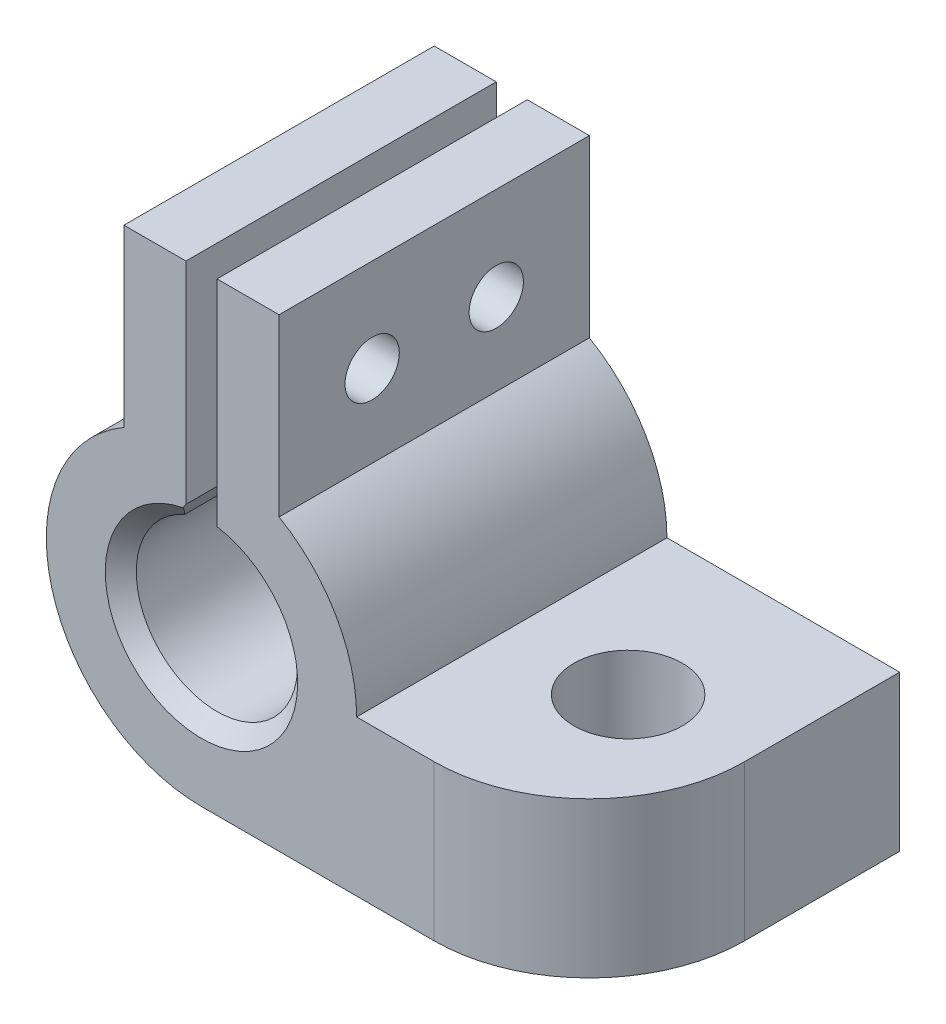
SolidWorks part; units mm, degrees
ref_plane "Płaszczyzna przednia" through (0, 0, 0) normal (0, 0, 1) x (1, 0, 0)
ref_plane "Płaszczyzna górna" through (0, 0, 0) normal (0, 1, 0) x (1, 0, 0)
ref_plane "Płaszczyzna prawa" through (0, 0, 0) normal (1, 0, 0) x (0, 0, -1)
sketch "Szkic1" plane through (0, 0, 0) normal (0, 0, 1) x (1, 0, 0)
  line L0 (-1, 5.1029) -> (-1, 9.9499)
  line L1 (1, 5.1029) -> (1, 9.9499)
  line L2 (0, 0) -> (0, 18.1037) construction
  line L3 (-1, 9.9499) -> (-1, 19.9499)
  line L4 (1, 9.9499) -> (1, 19.9499)
  line L5 (1, 19.9499) -> (5, 19.9499)
  line L6 (5, 19.9499) -> (5, 8.6603)
  line L7 (-1, 19.9499) -> (-5, 19.9499)
  line L8 (-5, 19.9499) -> (-5, 8.6603)
  circle A0 centre (0, 0) radius 5.2
  circle A1 centre (0, 0) radius 10
  dimension "D1" = 10.4
  dimension "D2" = 20
  dimension "D3" = 2
  dimension "D4" = 4
  dimension "D5" = 10
extrude "Dodanie-wyciągnięcie1" add sketch "Szkic1" along normal blind 20 contours A1 L1 A0 L0 | A1 L3 L7 L8 | A1 L6 L5 L4
chamfer "Sfazowanie1" distance 1 angle 45 3 edges at (0, -5.2, 20) (1, 5.1029, 10) (-1, 5.1029, 10)
sketch "Szkic2" plane through (5, 0, 0) normal (1, 0, 0) x (0, 0, -1)
  line L0 (-20, 19.9499) -> (-20, 8.6603) construction
  line L1 (-20, 19.9499) -> (0, 19.9499) construction
  circle A0 centre (-14, 13.9499) radius 1.75
  circle A1 centre (-6, 13.9499) radius 1.75
  dimension "D1" = 3.5
  dimension "D2" = 8
  dimension "D3" = 6
  dimension "D4" = 6
extrude "Wytnij-wyciągnięcie1" cut sketch "Szkic2" against normal blind 10
sketch "Szkic3" plane through (-5, 0, 0) normal (-1, 0, 0) x (0, 0, 1)
  line L1 (9.4641, 13.9499) -> (7.7321, 16.9499)
  line L2 (7.7321, 16.9499) -> (4.2679, 16.9499)
  line L3 (4.2679, 16.9499) -> (2.5359, 13.9499)
  line L4 (2.5359, 13.9499) -> (4.2679, 10.9499)
  line L5 (4.2679, 10.9499) -> (7.7321, 10.9499)
  line L6 (7.7321, 10.9499) -> (9.4641, 13.9499)
  line L7 (10.5359, 13.9499) -> (12.2679, 10.9499)
  line L8 (12.2679, 10.9499) -> (15.7321, 10.9499)
  line L9 (15.7321, 10.9499) -> (17.4641, 13.9499)
  line L10 (17.4641, 13.9499) -> (15.7321, 16.9499)
  line L11 (15.7321, 16.9499) -> (12.2679, 16.9499)
  line L12 (12.2679, 16.9499) -> (10.5359, 13.9499)
  circle A0 centre (14, 13.9499) radius 1.75 construction
  circle A1 centre (6, 13.9499) radius 1.75 construction
  circle A2 centre (14, 13.9499) radius 1.75
  circle A3 centre (6, 13.9499) radius 1.75
  circle A4 centre (6, 13.9499) radius 3 construction
  circle A5 centre (14, 13.9499) radius 3 construction
  dimension "D1" = 6
extrude "Wytnij-wyciągnięcie2" cut sketch "Szkic3" against normal blind 1
sketch "Szkic4" plane through (0, 0, 20) normal (0, 0, 1) x (1, 0, 0)
  line L0 (0, -10) -> (25, -10)
  line L1 (25, -10) -> (25, 0)
  line L2 (25, 0) -> (10, 0)
  arc A0 (-5, 8.6603) -> (5, 8.6603) centre (0, 0) ccw construction
  arc A1 (-5, 8.6603) -> (5, 8.6603) centre (0, 0) ccw
  arc M8 (-5, 8.6603) -> (5, 8.6603) centre (0, 0) ccw
  dimension "D1" = 25
extrude "Dodanie-wyciągnięcie2" add sketch "Szkic4" against normal blind 20 contours L1 L2 L0 M8
sketch "Szkic5" plane through (0, 0, 0) normal (0, 1, 0) x (1, 0, 0)
  line L0 (25, -10) -> (23.319, -10) construction
  line L1 (25, 0) -> (25, -20) construction
  line L2 (17.5, 0) -> (17.5, -3.2931) construction
  line L3 (25, 0) -> (10, 0) construction
  circle A0 centre (17.5, -10) radius 3.5
  dimension "D1" = 7
extrude "Wytnij-wyciągnięcie3" cut sketch "Szkic5" against normal blind 20
fillet "Zaokrąglenie1" radius 10 1 edges at (25, -5, 20)
